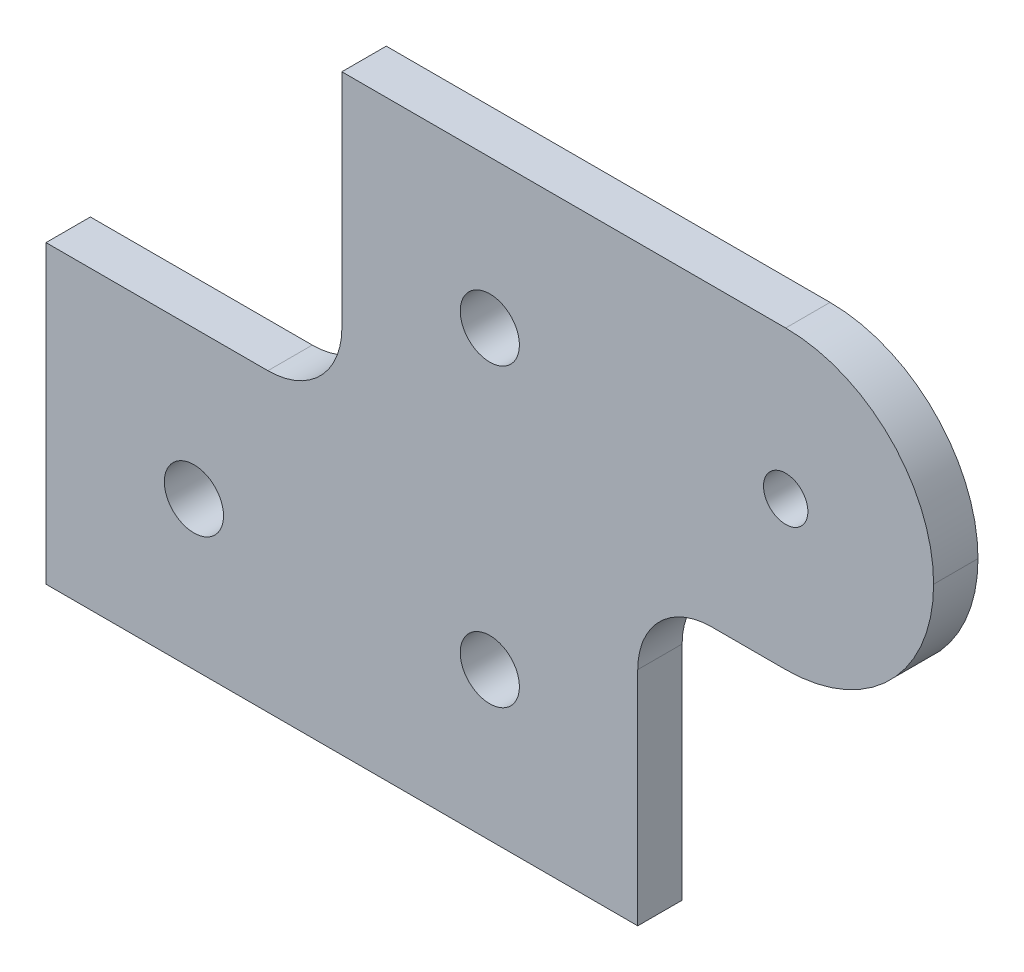
SolidWorks part; units mm, degrees
ref_plane "Plano frontal" through (0, 0, 0) normal (0, 0, 1) x (1, 0, 0)
ref_plane "Plano superior" through (0, 0, 0) normal (0, 1, 0) x (1, 0, 0)
ref_plane "Plano direito" through (0, 0, 0) normal (1, 0, 0) x (0, 0, -1)
sketch "Esboço1" plane through (0, 0, 0) normal (0, 0, 1) x (1, 0, 0)
  line L0 (0, 10) -> (40, 10) construction
  line L1 (0, 0) -> (40, 0)
  line L2 (0, 0) -> (0, 20)
  line L3 (0, 20) -> (40, 20)
  line L4 (40, 0) -> (40, 20)
  line L5 (40, 0) -> (20, 0)
  line L6 (40, 0) -> (40, 40)
  line L7 (40, 40) -> (20, 40)
  line L8 (20, 0) -> (20, 40)
  line L9 (20, 40) -> (60, 40)
  line L10 (20, 40) -> (20, 20)
  line L11 (20, 20) -> (60, 20)
  line L12 (60, 40) -> (60, 20)
  line L13 (30, 40) -> (30, 0) construction
  line L14 (60, 30) -> (20, 30) construction
  line L15 (10, 20) -> (10, 0) construction
  line L16 (50, 40) -> (50, 20) construction
  circle A0 centre (10, 10) radius 2
  circle A1 centre (30, 10) radius 2
  circle A2 centre (30, 30) radius 2
  circle A3 centre (50, 30) radius 1.5
  dimension "D6" = 4
  dimension "D8" = 3
  dimension "D1" = 20
  dimension "D2" = 40
  dimension "D3" = 40
  dimension "D4" = 40
  dimension "D5" = 10
  dimension "D7" = 10
extrude "Ressalto-extrusão1" add sketch "Esboço1" along normal blind 3 contours L1 L8 L3 L2 A0 | L8 L1 L4 L3 A1 | L8 L3 L6 L7 A2 | L12 L9 L6 L11 A3 region at (0.2828, 10, 0) region at (20.2828, 10, 0) region at (20.2828, 30, 0) region at (40.2828, 30, 0)
fillet "Filete1" radius 10 2 edges at (60, 20, 1.5) (60, 40, 1.5)
fillet "Filete2" radius 5 2 edges at (40, 20, 1.5) (20, 20, 1.5)
